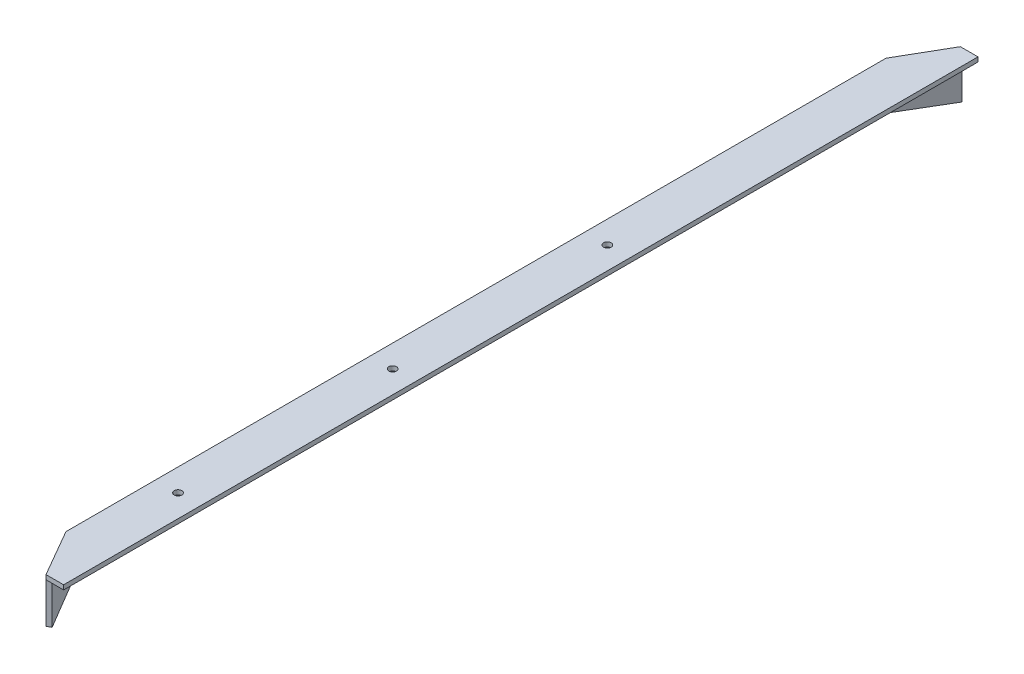
SolidWorks part; units mm, degrees
material "1.0116 (S235J2G3)"
ref_plane "Front Plane" through (0, 0, 0) normal (0, 0, 1) x (1, 0, 0)
ref_plane "Top Plane" through (0, 0, 0) normal (0, 1, 0) x (1, 0, 0)
ref_plane "Right Plane" through (0, 0, 0) normal (1, 0, 0) x (0, 0, -1)
sketch "Sketch1" plane through (0, 0, 0) normal (0, 0, 1) x (1, 0, 0)
  line L6 (0, 0) -> (0, 70)
  line L7 (0, 70) -> (70, 70)
  line L8 (70, 70) -> (70, 63)
  line L9 (70, 63) -> (7, 63)
  line L10 (7, 63) -> (7, 0)
  line L11 (7, 0) -> (0, 0)
  dimension "D1" = 70
  dimension "D2" = 70
  dimension "D3" = 7
  dimension "D4" = 7
extrude "Boss-Extrude1" add sketch "Sketch1" along normal blind 640
sketch "Sketch21" plane through (0, 0, 0) normal (0, 0, -1) x (-1, 0, 0)
  line L0 (0, 70) -> (-70, 70) construction
  line L1 (-70, 70) -> (-70, 0) construction
  line L2 (-70, 0) -> (0, 0) construction
  line L3 (0, 0) -> (0, 69.2595) construction
sketch "Sketch23" plane through (0, 0, 0) normal (0, 1, 0) x (1, 0, 0)
  line L0 (0, -640) -> (42.5, -713.6122)
  line L1 (42.5, -713.6122) -> (48.5622, -710.1122)
  line L2 (48.5622, -710.1122) -> (7, -640)
  line L3 (7, -640) -> (0, -640)
  line L4 (0, -38.5) -> (0, 38.5) construction
  dimension "D1" = 7
  dimension "D2" = 210
  dimension "D3" = 85
extrude "Boss-Extrude2" add sketch "Sketch23" along normal blind 63
sketch "Sketch25" plane through (0, 63, 0) normal (0, 1, 0) x (1, 0, 0)
  line L0 (70, -640) -> (0, -640)
  line L1 (70, -640) -> (70, 0) construction
  line L2 (7, -640) -> (70, -640) construction
  line L3 (0, -640) -> (42.5, -713.6122) construction
  line L4 (0, -640) -> (42.5, -713.6122)
  line L5 (42.5, -713.6122) -> (48.5622, -710.1122) construction
  line L6 (42.5, -713.6122) -> (70, -713.6122)
  line L7 (70, -713.6122) -> (70, -640)
extrude "Boss-Extrude3" add sketch "Sketch25" along normal blind 7
sketch "Sketch26" plane through (-275.5567, 0, 163.3488) normal (0.8602, 0, -0.5099) x (-0.5099, 0, -0.8602)
  line L0 (-635.6125, 0) -> (-554.1071, 0) construction
  line L1 (-635.6125, 63) -> (-635.6125, 0) construction
  line L2 (-554.1071, 0) -> (-554.1071, 63) construction
  circle A0 centre (-614.3625, 31.5) radius 6
  circle A1 centre (-575.3571, 31.5) radius 6
  dimension "D1" = 12
  dimension "D2" = 12
  dimension "D3" = 31.5
  dimension "D4" = 31.5
  dimension "D5" = 21.25
  dimension "D6" = 21.25
mirror "Mirror1" about plane through (0, 0, 0) normal (0, 0, 1) of bodies 113 116
sketch "Sketch28" plane through (0, 70, 0) normal (0, 1, 0) x (1, 0, 0)
  line L0 (70, -713.6122) -> (70, 713.6122) construction
  circle A0 centre (35, -500) radius 6
  circle A1 centre (35, -165) radius 6
  circle A2 centre (35, 170) radius 6
  point P6 (0, 0)
  point P7 (0, 0)
  point P8 (0, 0)
  dimension "D1" = 12
  dimension "D2" = 12
  dimension "D3" = 12
  dimension "D4" = 335
  dimension "D5" = 335
  dimension "D6" = 500
  dimension "D7" = 35
  dimension "D8" = 35
  dimension "D9" = 35
extrude "Cut-Extrude1" cut sketch "Sketch28" against normal blind 10 and the other way blind 10
